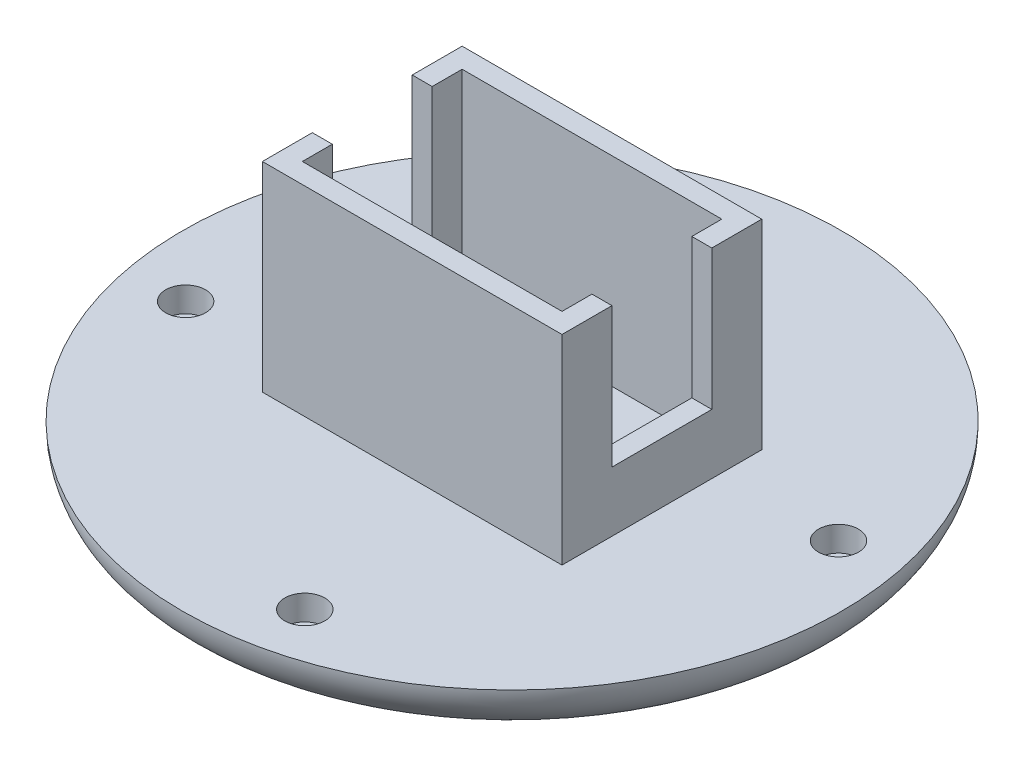
SolidWorks part; units mm, degrees
ref_plane "Front Plane" through (0, 0, 0) normal (0, 0, 1) x (1, 0, 0)
ref_plane "Top Plane" through (0, 0, 0) normal (0, 1, 0) x (1, 0, 0)
ref_plane "Right Plane" through (0, 0, 0) normal (1, 0, 0) x (0, 0, -1)
sketch "Sketch1" plane through (0, 0, 0) normal (0, 1, 0) x (1, 0, 0)
  circle A0 centre (0, 0) radius 33
extrude "Boss-Extrude1" add sketch "Sketch1" along normal blind 5
sketch "Sketch2" plane through (0, 5, 0) normal (0, 1, 0) x (1, 0, 0)
  circle A0 centre (-26.72, -5.9654) radius 2
  circle A1 centre (-5.9654, 26.72) radius 2
  circle A2 centre (26.72, 5.9654) radius 2
  circle A3 centre (5.9654, -26.72) radius 2
  point P11 (0, 0)
  dimension "D1" = 4
extrude "Cut-Extrude1" cut sketch "Sketch2" against normal blind 2.5
fillet "Fillet1" radius 5 1 edges at (0, 0, 33)
sketch "Sketch3" plane through (0, 5, 0) normal (0, 1, 0) x (1, 0, 0)
  line L1 (15, -10) -> (-15, -10)
  line L2 (15, -10) -> (15, 10)
  line L3 (15, 10) -> (-15, 10)
  line L4 (-15, -10) -> (-15, 10)
  line L5 (13, -8) -> (-13, -8)
  line L6 (13, -8) -> (13, 8)
  line L7 (13, 8) -> (-13, 8)
  line L8 (-13, -8) -> (-13, 8)
  circle A0 centre (0, 0) radius 33 construction
  dimension "D1" = 30
  dimension "D2" = 20
  dimension "D3" = 2
  dimension "D4" = 2
  dimension "D5" = 2
  dimension "D6" = 2
  dimension "D7" = 13
  dimension "D8" = 8
extrude "Boss-Extrude2" add sketch "Sketch3" along normal blind 20
sketch "Sketch4" plane through (15, 0, 0) normal (1, 0, 0) x (0, 0, -1)
  line L0 (-10, 25) -> (10, 25) construction
  line L1 (-5, 25) -> (5, 25)
  line L2 (-5, 25) -> (-5, 11)
  line L3 (-5, 11) -> (5, 11)
  line L4 (5, 25) -> (5, 11)
  line L5 (-10, 25) -> (-10, 5) construction
  line L6 (10, 25) -> (10, 5) construction
  line L7 (-10, 5) -> (10, 5) construction
  dimension "D1" = 5
  dimension "D2" = 5
  dimension "D3" = 6
extrude "Cut-Extrude2" cut sketch "Sketch4" against normal blind 60
sketch "Sketch5" plane through (0, 0, 0) normal (0, -1, 0) x (1, 0, 0)
  text T0 "RHOCAN" font "Century Gothic" height 15.5
extrude "Cut-Extrude3" cut sketch "Sketch5" against normal blind 2
